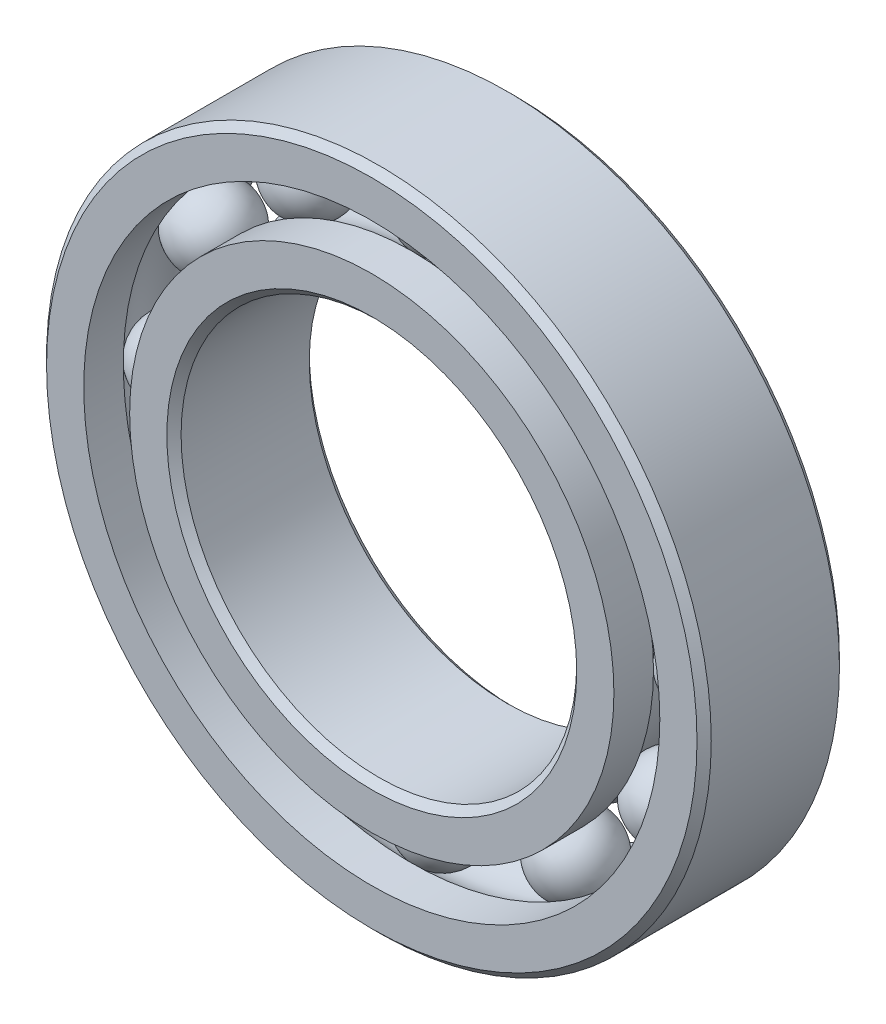
SolidWorks part; units mm, degrees
ref_plane "Front Plane" through (0, 0, 0) normal (0, 0, 1) x (1, 0, 0)
ref_plane "Top Plane" through (0, 0, 0) normal (0, 1, 0) x (1, 0, 0)
ref_plane "Right Plane" through (0, 0, 0) normal (1, 0, 0) x (0, 0, -1)
sketch "Sketch1" plane through (0, 0, 0) normal (1, 0, 0) x (0, 0, -1)
  line L0 (-4.5, 0) -> (4.5, 0) construction
  line L1 (0, 21) -> (0, -21) construction
  line L2 (4.05, 21) -> (-4.05, 21)
  line L3 (-4.05, 21) -> (-4.5, 20.55)
  line L4 (-4.5, 20.55) -> (-4.5, 18.2005)
  line L5 (-4.5, 18.2005) -> (-2, 18.2005)
  line L6 (4.5, 18.2005) -> (2, 18.2005)
  line L7 (4.5, 20.55) -> (4.5, 18.2005)
  line L8 (4.05, 21) -> (4.5, 20.55)
  line L9 (0, 21) -> (0, 16.75) construction
  line L10 (0, 16.75) -> (0, 12.5) construction
  arc A0 (-2, 18.2005) -> (2, 18.2005) centre (0, 16.75) cw
  point P14 (0, 12.5)
  dimension "Width" = 9
  dimension "OD" = 42
  dimension "D1" = 45
  dimension "D2" = 0.45
  dimension "Shaft Dia" = 25
  dimension "D3" = 4
  dimension "D4" = 1.4505
revolve "Revolve1" add sketch "Sketch1" angle 360 about L0
sketch "Sketch3" plane through (0, 0, 0) normal (1, 0, 0) x (0, 0, -1)
  line L0 (-4.5, 15.2995) -> (-2, 15.2995)
  line L1 (0, 21) -> (0, -21) construction
  line L2 (-4.5, 20.55) -> (-4.5, 18.2005) construction
  line L3 (-4.5, 15.2995) -> (-4.5, 12.95)
  line L4 (-4.05, 21) -> (-4.5, 20.55) construction
  line L5 (-4.5, 12.95) -> (-4.05, 12.5)
  line L6 (-4.05, 12.5) -> (4.05, 12.5)
  line L7 (4.05, 21) -> (4.05, -21) construction
  line L8 (4.05, 12.5) -> (4.5, 12.95)
  line L9 (4.5, -20.55) -> (4.5, 20.55) construction
  line L10 (4.5, 12.95) -> (4.5, 15.2995)
  line L11 (4.5, 15.2995) -> (2, 15.2995)
  line L13 (4.05, 21) -> (4.5, 20.55) construction
  arc A0 (2, 18.2005) -> (-2, 18.2005) centre (0, 16.75) ccw construction
  arc A1 (2, 15.2995) -> (-2, 15.2995) centre (0, 16.75) cw
revolve "Revolve3" add sketch "Sketch3" angle 360 about L0
sketch "Sketch4" plane through (0, 0, 0) normal (1, 0, 0) x (0, 0, -1)
  line L0 (-2.4706, 16.75) -> (2.4706, 16.75)
  arc A2 (-2.4706, 16.75) -> (2.4706, 16.75) centre (0, 16.75) cw
  arc A3 (2, 18.2005) -> (-2, 18.2005) centre (0, 16.75) ccw construction
revolve "Revolve4" add sketch "Sketch4" angle 360 about L0
ref_axis "Axis1" through (0, 0, -4.5) along (0, 0, 1)
pattern_circular "CirPattern1" count 12 every 30 about axis through (0, 0, -4.5) along (0, 0, 1) of bodies 104
sketch "Sketch5" plane through (0, 0, 0) normal (1, 0, 0) x (0, 0, -1)
  line L0 (-4.5, 18.2005) -> (-2, 18.2005) construction
  line L1 (-4.275, 18.2005) -> (-2.4706, 18.2005)
  line L2 (-4.275, 18.2005) -> (-4.275, 15.2995)
  line L3 (-4.275, 15.2995) -> (-2.4706, 15.2995)
  line L4 (-2.4706, 18.2005) -> (-2.4706, 15.2995)
  line L5 (-4.5, 15.2995) -> (-2, 15.2995) construction
  line L6 (4.5, 18.2005) -> (2, 18.2005) construction
  line L7 (4.275, 18.2005) -> (2.4706, 18.2005)
  line L8 (4.275, 18.2005) -> (4.275, 15.2995)
  line L9 (4.275, 15.2995) -> (2.4706, 15.2995)
  line L10 (2.4706, 18.2005) -> (2.4706, 15.2995)
  line L11 (4.5, 15.2995) -> (2, 15.2995) construction
  line L12 (-4.05, 21) -> (-4.5, 20.55) construction
  point P18 (-4.275, 20.775)
equation "\"D2@Sketch1\" = \"Width@Sketch1\"*.05"
equation "\"D3@Sketch1\" = \"Width@Sketch1\"/2.25"
equation "\"D4@Sketch1\" = (((\"OD@Sketch1\"-\"Width@Sketch1\")/2)/3.25)/3.5"
equation "\"D2@CirPattern1\" = 360/\"Balls@CirPattern1\""
